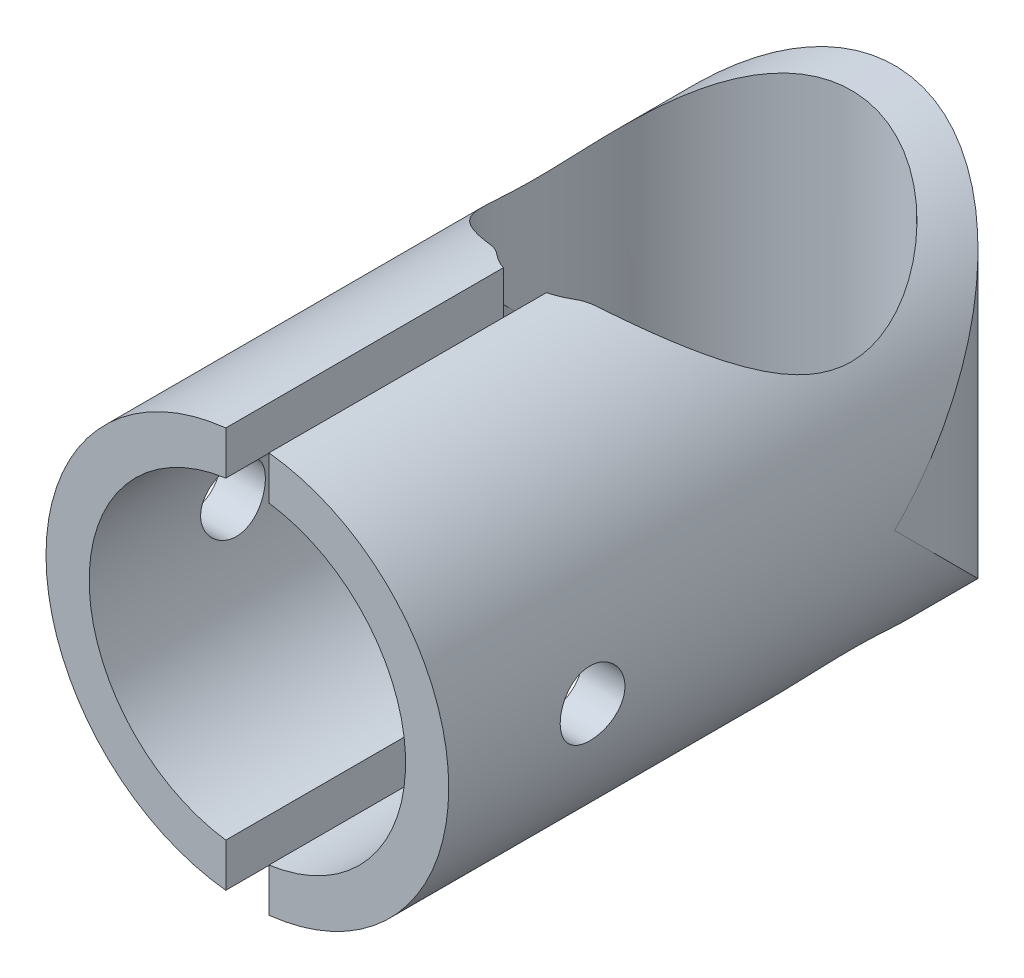
SolidWorks part; units mm, degrees
material "Сплав 2024"
ref_plane "Спереди" through (0, 0, 0) normal (0, 0, 1) x (1, 0, 0)
ref_plane "Сверху" through (0, 0, 0) normal (0, 1, 0) x (1, 0, 0)
ref_plane "Справа" through (0, 0, 0) normal (1, 0, 0) x (0, 0, -1)
sketch "Эскиз1" plane through (0, 0, 0) normal (0, 0, 1) x (1, 0, 0)
  circle A0 centre (0, 0) radius 14
  dimension "D1" = 28
extrude "Бобышка-Вытянуть1" add sketch "Эскиз1" along normal blind 45
ref_plane "Плоскость1" through (0, 14, 0) normal (0, 1, 0) x (1, 0, 0)
sketch "Эскиз2" plane through (0, 14, 0) normal (0, 1, 0) x (1, 0, 0)
  line L0 (0, 0) -> (0, -45) construction
  line L1 (-14, -45) -> (14, -45) construction
  line L2 (14, 0) -> (-14, 0) construction
  line L8 (-1.5, -24.8972) -> (-1.5, -45)
  line L9 (-1.5, -45) -> (1.5, -45)
  line L10 (1.5, -24.8972) -> (1.5, -45)
  line L11 (-1.5, -24.8972) -> (1.5, -45) construction
  line L12 (-1.5, -45) -> (1.5, -24.8972) construction
  arc A0 (1.5, -24.8972) -> (-1.5, -24.8972) centre (0, -14) ccw
  point P9 (0, -12.5)
  point P10 (0, -34.9486)
  point P17 (12.5, -12.5)
  dimension "D1" = 22
  dimension "D3" = 3
  dimension "D2" = 14
extrude "Вырез-Вытянуть1" cut sketch "Эскиз2" against normal through all
sketch "Эскиз3" plane through (0, 14, 0) normal (0, 1, 0) x (1, 0, 0)
  line L0 (14, -45) -> (14, 0) construction
  line L1 (14, 0) -> (-14, 0) construction
  line L2 (0, 0) -> (14, 0)
  line L3 (14, 0) -> (14, -14)
  arc A0 (14, -14) -> (0, 0) centre (0, -14) ccw
extrude "Вырез-Вытянуть2" cut sketch "Эскиз3" against normal through all
mirror "Зеркальное отражение1" about plane through (0, 0, 0) normal (1, 0, 0) of "Вырез-Вытянуть2"
sketch "Эскиз5" plane through (0, 0, 45) normal (0, 0, 1) x (1, 0, 0)
  circle A0 centre (0, 0) radius 11
  dimension "D1" = 22
extrude "Вырез-Вытянуть3" cut sketch "Эскиз5" against normal up to next
ref_plane "Плоскость2" through (-14, 0, 0) normal (-1, 0, 0) x (0, 0, 1)
sketch "Эскиз7" plane through (-14, 0, 0) normal (-1, 0, 0) x (0, 0, 1)
  line L0 (45, 0) -> (0, 0) construction
  line L1 (45, -13.9194) -> (45, 13.9194) construction
  line L2 (35, 13.9194) -> (35, -13.9194) construction
  line L3 (45, 13.9194) -> (24.8972, 13.9194) construction
  line L4 (24.8972, -13.9194) -> (45, -13.9194) construction
  dimension "D1" = 10
hole_wizard "Отверстие с зазором M41" positions "Эскиз9" profile "Эскиз8" hole size "M4" standard "Ansi Metric" end condition through all
sketch "Эскиз9" plane through (-14, 0, 0) normal (-1, 0, 0) x (0, 0, 1)
  line L0 (45, 0) -> (0, 0) construction
  line L1 (35, 13.9194) -> (35, -13.9194) construction
  point P0 (35, 0)
sketch "Эскиз8" plane through (-14, 0, 35) normal (0, 1, 0) x (0, 0, 1)
  line L0 (0, 0) -> (0, 28)
  line L1 (0, 28) -> (2.25, 28)
  line L2 (2.25, 28) -> (2.25, 0)
  line L5 (2.25, 0) -> (0, 0)
  line L11 (0, -6.35) -> (0, 107.95) construction
  dimension "Диаметр сквозного отверстия" = 4.5
  dimension "Глубина сквозного отверстия" = 28
sketch "Эскиз10" plane through (0, 14, 0) normal (0, 1, 0) x (1, 0, 0)
  line L0 (0, 0) -> (0, -50) construction
  circle A0 centre (0, -22) radius 4
  arc A1 (14, -14) -> (-14, -14) centre (0, -14) ccw construction
  arc A2 (1.5, -24.8972) -> (-1.5, -24.8972) centre (0, -14) ccw construction
  dimension "D1" = 8
  dimension "D2" = 8
extrude "Вырез-Вытянуть5" cut sketch "Эскиз10" against normal through all
fillet "Скругление2" radius 3 12 edges at (2.3895, 13.7946, 25.2079) (3.0714, 12.1107, 24.5625) (3.0714, -12.1107, 24.5625) (1.6626, -10.8736, 25.6381) (-2.3895, -13.7946, 25.2079) (-3.0714, -12.1107, 24.5625) (-3.0714, 12.1107, 24.5625) (-8.7973, -6.6036, 20.6036) (-1.6626, 10.8736, 25.6381) (8.7973, 6.6036, 20.6036) (1.3936, -13.9305, 3.0886) (-1.3936, 13.9305, 3.0886)
